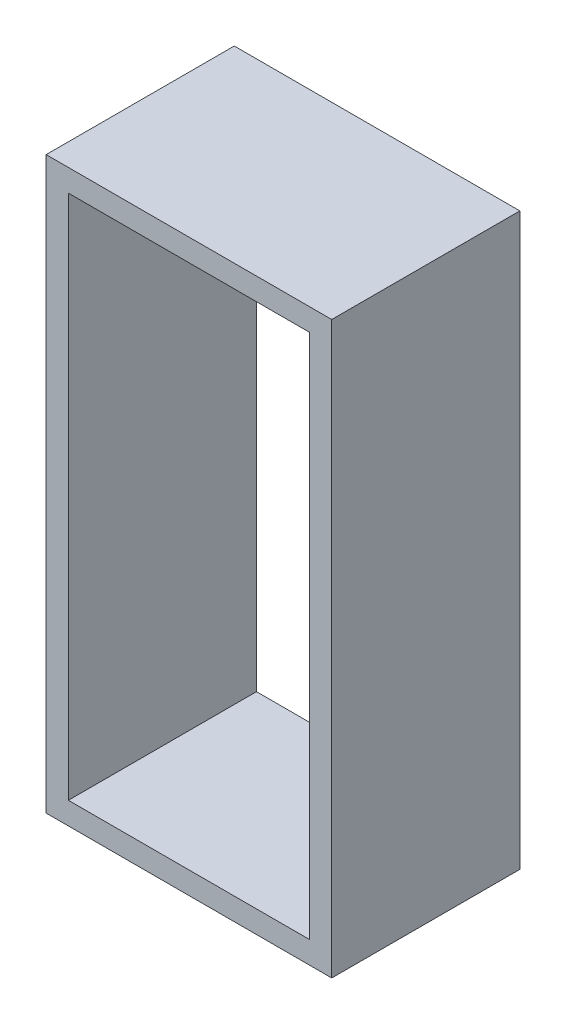
SolidWorks part; units mm, degrees
ref_plane "Front Plane" through (0, 0, 0) normal (0, 0, 1) x (1, 0, 0)
ref_plane "Top Plane" through (0, 0, 0) normal (0, 1, 0) x (1, 0, 0)
ref_plane "Right Plane" through (0, 0, 0) normal (1, 0, 0) x (0, 0, -1)
sketch "Strap Sketch" plane through (0, 0, 0) normal (0, 0, 1) x (1, 0, 0)
  line L0 (-14.55, -43.75) -> (4.73, -43.75)
  line L1 (4.73, -43.75) -> (4.73, -5.25)
  line L2 (4.73, -5.25) -> (-14.55, -5.25)
  line L3 (-14.55, -5.25) -> (-14.55, -43.75)
  line L4 (-13.05, -42.25) -> (3.23, -42.25)
  line L5 (3.23, -42.25) -> (3.23, -6.75)
  line L6 (3.23, -6.75) -> (-13.05, -6.75)
  line L7 (-13.05, -6.75) -> (-13.05, -42.25)
extrude "Strap" add sketch "Strap Sketch" along normal mid plane 12.7
ref_axis "Engine Axis" through (5.694, 0, 0) along (-1, 0, 0)
